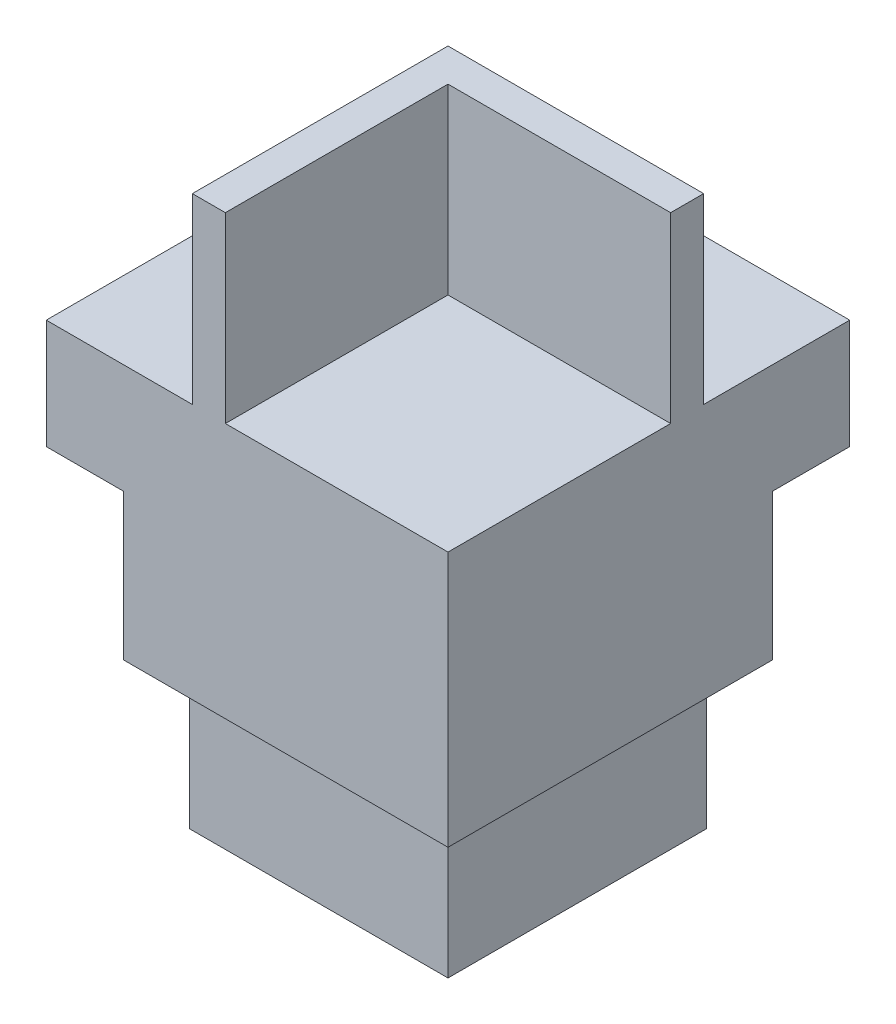
SolidWorks part; units mm, degrees
ref_plane "Front Plane" through (0, 0, 0) normal (0, 0, 1) x (1, 0, 0)
ref_plane "Top Plane" through (0, 0, 0) normal (0, 1, 0) x (1, 0, 0)
ref_plane "Right Plane" through (0, 0, 0) normal (1, 0, 0) x (0, 0, -1)
sketch "Sketch7" plane through (0, 0, 0) normal (0, 1, 0) x (1, 0, 0)
  line L1 (-15.54, -25.3407) -> (11.96, -25.3407)
  line L2 (-15.54, -25.3407) -> (-15.54, -52.8407)
  line L3 (-15.54, -52.8407) -> (11.96, -52.8407)
  line L4 (11.96, -25.3407) -> (11.96, -52.8407)
  dimension "D1" = 27.5
  dimension "D2" = 27.5
extrude "Boss-Extrude6" add sketch "Sketch7" along normal blind 40 separate body
sketch "Sketch8" plane through (0, 40, 0) normal (0, 1, 0) x (1, 0, 0)
  line L1 (11.96, -52.8407) -> (-3.28, -52.8407)
  line L2 (11.96, -52.8407) -> (11.96, -37.6007)
  line L3 (11.96, -37.6007) -> (-3.28, -37.6007)
  line L4 (-3.28, -52.8407) -> (-3.28, -37.6007)
  dimension "D1" = 15.24
  dimension "D2" = 15.24
extrude "Cut-Extrude2" cut sketch "Sketch8" against normal blind 12.5
sketch "Sketch9" plane through (0, 0, 0) normal (0, -1, 0) x (1, 0, 0)
  line L1 (11.96, 52.8407) -> (-10.24, 52.8407)
  line L2 (11.96, 52.8407) -> (11.96, 30.6407)
  line L3 (11.96, 30.6407) -> (-10.24, 30.6407)
  line L4 (-10.24, 52.8407) -> (-10.24, 30.6407)
  line L5 (11.96, 52.8407) -> (-15.54, 52.8407)
  line L6 (11.96, 52.8407) -> (11.96, 25.3407)
  line L7 (11.96, 25.3407) -> (-15.54, 25.3407)
  line L8 (-15.54, 52.8407) -> (-15.54, 25.3407)
  line M5 (-15.54, 52.8407) -> (-15.54, 25.3407)
  line M6 (-15.54, 25.3407) -> (11.96, 25.3407)
  line M7 (11.96, 25.3407) -> (11.96, 52.8407)
  line M8 (11.96, 52.8407) -> (-15.54, 52.8407)
  dimension "D1" = 22.2
  dimension "D2" = 22.2
extrude "Cut-Extrude3" cut sketch "Sketch9" against normal blind 20 contours L4 L3 M8 M5 M6 M7 region at (-10.6289, 0, 41.7407)
sketch "Sketch10" plane through (0, 0, 0) normal (0, -1, 0) x (1, 0, 0)
  line L0 (-10.24, 41.7407) -> (11.96, 41.7407) construction
  line L2 (-10.24, 52.8407) -> (-10.24, 30.6407) construction
  line L3 (11.96, 52.8407) -> (11.96, 30.6407) construction
  line L5 (-7.99, 50.5907) -> (9.71, 50.5907)
  line L6 (-7.99, 50.5907) -> (-7.99, 32.8907)
  line L7 (-7.99, 32.8907) -> (9.71, 32.8907)
  line L8 (9.71, 50.5907) -> (9.71, 32.8907)
  line L9 (-7.99, 50.5907) -> (9.71, 32.8907) construction
  line L10 (-7.99, 32.8907) -> (9.71, 50.5907) construction
  line L11 (-10.24, 52.8407) -> (11.96, 52.8407)
  line L12 (-10.24, 52.8407) -> (-10.24, 30.6407)
  line L13 (-10.24, 30.6407) -> (11.96, 30.6407)
  line L14 (11.96, 52.8407) -> (11.96, 30.6407)
  line L15 (-10.24, 52.8407) -> (11.96, 30.6407) construction
  line L16 (-10.24, 30.6407) -> (11.96, 52.8407) construction
  point P6 (0.86, 41.7407)
  point P11 (0.86, 41.7407)
  dimension "D1" = 17.7
  dimension "D2" = 17.7
extrude "Cut-Extrude4" cut sketch "Sketch10" against normal blind 10
sketch "Sketch11" plane through (0, 40, 0) normal (0, 1, 0) x (1, 0, 0)
  line L1 (11.96, -25.3407) -> (-10.5577, -25.3407)
  line L2 (11.96, -25.3407) -> (11.96, -35.3407)
  line L3 (11.96, -35.3407) -> (-5.54, -35.3407)
  line L5 (-15.54, -52.8407) -> (-5.54, -52.8407)
  line L6 (-15.54, -52.8407) -> (-15.54, -25.3407)
  line L7 (-15.54, -25.3407) -> (-4.5646, -25.3407)
  line L8 (-5.54, -52.8407) -> (-5.54, -35.3407)
  line M6 (11.96, -37.6007) -> (11.96, -25.3407)
  line M7 (11.96, -25.3407) -> (-15.54, -25.3407)
  line M8 (-15.54, -25.3407) -> (-15.54, -52.8407)
  line M9 (-15.54, -52.8407) -> (-3.28, -52.8407)
  dimension "D1" = 10
  dimension "D2" = 10
extrude "Cut-Extrude5" cut sketch "Sketch11" against normal blind 12.5 contours L8 L3 L1 M9 M6 M7 M8 region at (11.5711, 40, 30.3407)
